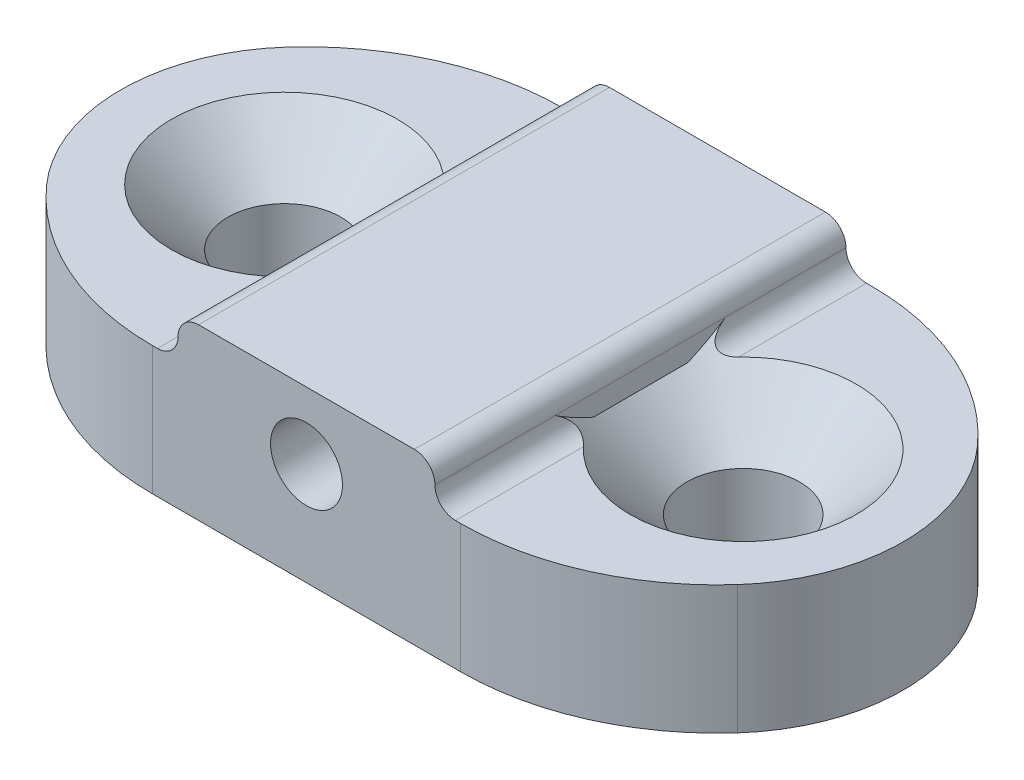
SolidWorks part; units mm, degrees
ref_plane "Front Plane" through (0, 0, 0) normal (0, 0, 1) x (1, 0, 0)
ref_plane "Top Plane" through (0, 0, 0) normal (0, 1, 0) x (1, 0, 0)
ref_plane "Right Plane" through (0, 0, 0) normal (1, 0, 0) x (0, 0, -1)
sketch "Sketch1" plane through (0, 0, 0) normal (0, 1, 0) x (1, 0, 0)
  line L1 (0, 0) -> (16, 0)
  line L2 (0, 0) -> (0, 8)
  line L3 (0, 8) -> (16, 8)
  line L4 (16, 0) -> (16, 8)
  dimension "D1" = 16
  dimension "D2" = 8
extrude "Boss-Extrude1" add sketch "Sketch1" along normal blind 2.5
sketch "Sketch2" plane through (0, 0, 0) normal (0, 0, 1) x (1, 0, 0)
  line L0 (0, 2.5) -> (16, 2.5) construction
  line L1 (5.5, 2.5) -> (10.5, 2.5)
  line L2 (5.5, 2.5) -> (5.5, 3.3)
  line L3 (5.5, 3.3) -> (10.5, 3.3)
  line L4 (10.5, 2.5) -> (10.5, 3.3)
  line L5 (8, 0) -> (8, 3.3) construction
  line L6 (0, 0) -> (16, 0) construction
  point P10 (8, 3.3)
  dimension "D1" = 0.8
  dimension "D2" = 5
extrude "Boss-Extrude2" add sketch "Sketch2" against normal up to surface (8 mm away) up to face at (8, 1.25, -8)
sketch "Sketch3" plane through (0, 0, 0) normal (0, 0, 1) x (1, 0, 0)
  line L0 (8, 3.3) -> (8, 0) construction
  line L1 (10.5, 3.3) -> (5.5, 3.3) construction
  line L2 (0, 0) -> (16, 0) construction
  circle A0 centre (8, 2) radius 0.7
  point P9 (8, 3.3)
  dimension "D1" = 1.4
  dimension "D2" = 2
extrude "Cut-Extrude1" cut sketch "Sketch3" against normal through all both and the other way through all
sketch "Sketch4" plane through (0, 2.5, 0) normal (0, 1, 0) x (1, 0, 0)
  line L0 (12.5, 8) -> (12.5, 4) construction
  line L1 (16, 8) -> (10.5, 8) construction
  line L2 (3.5, 8) -> (3.5, 4) construction
  line L3 (5.5, 8) -> (0, 8) construction
  line L4 (3.5, 4) -> (12.5, 4) construction
  line L5 (16, 0) -> (16, 8) construction
  line L6 (0, 8) -> (0, 0) construction
  point P12 (16, 4)
  dimension "D1" = 3.5
  dimension "D2" = 3.5
hole_wizard "CSK for M2 Countersunk Flat Head Screw1" positions "Sketch5" profile "Sketch6" countersink size "M2" standard "ISO" end condition through all
sketch "Sketch5" plane through (0, 2.5, 0) normal (0, 1, 0) x (1, 0, 0)
  point P0 (3.5711, 4)
  point P2 (12.5, 4)
sketch "Sketch6" plane through (3.5711, 2.5, -4) normal (1, 0, 0) x (0, 0, 1)
  line L0 (0, 0) -> (0, 2.5)
  line L1 (0, 2.5) -> (1.1, 2.5)
  line L2 (1.1, 2.5) -> (1.1, 1.1)
  line L3 (1.1, 1.1) -> (2.2, 0)
  line L5 (2.2, 0) -> (0, 0)
  line L6 (-1.1, 1.1) -> (-2.2, 0) construction
  line L11 (0, -6.35) -> (0, 107.95) construction
  dimension "Thru Hole Dia." = 2.2
  dimension "Thru Hole Depth" = 2.5
  dimension "Near C'Sink Dia." = 4.4
  dimension "Near C'Sink Angle" = 90
fillet "Fillet1" radius 0.4 6 edges at (10.5, 2.5, -6.4583) (10.5, 2.5, -1.5417) (10.5, 3.3, -4) (5.5, 3.3, -4) (5.5, 2.5, -1.471) (5.5, 2.5, -6.529)
fillet "Fillet2" radius 5 4 edges at (16, 1.25, 0) (16, 1.25, -8) (0, 1.25, -8) (0, 1.25, 0)
fillet "Fillet3" radius 3.5 2 edges at (0.101, 1.25, -4) (15.899, 1.25, -4)
